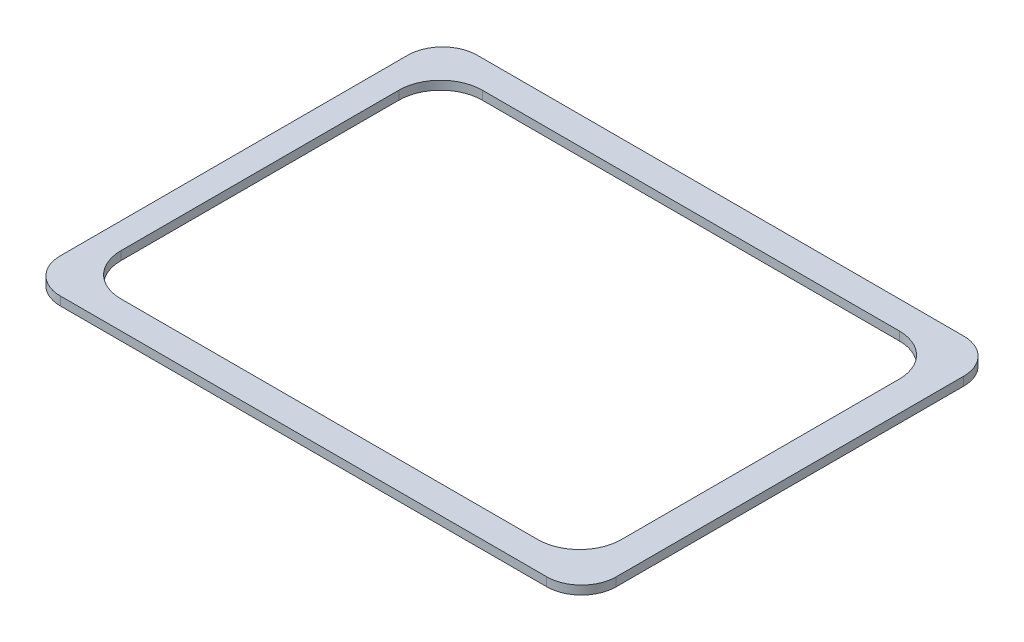
SolidWorks part; units mm, degrees
ref_plane "Front Plane" through (0, 0, 0) normal (0, 0, 1) x (1, 0, 0)
ref_plane "Top Plane" through (0, 0, 0) normal (0, 1, 0) x (1, 0, 0)
ref_plane "Right Plane" through (0, 0, 0) normal (1, 0, 0) x (0, 0, -1)
sketch "Sketch1" plane through (0, 6.35, 0) normal (0, 1, 0) x (1, 0, 0)
  line L19 (90.75, -50.8) -> (90.75, 0)
  line L25 (90.75, -50.8) -> (90.75, 0)
  line L27 (90.75, 0) -> (90.75, 50.8)
  line L44 (101.6, -63.5) -> (101.6, 63.5) construction
  line L45 (88.9, 76.2) -> (-88.9, 76.2) construction
  line L46 (-101.6, 63.5) -> (-101.6, -63.5) construction
  line L47 (-88.9, -76.2) -> (88.9, -76.2) construction
  line L52 (101.6, -63.5) -> (101.6, 63.5)
  line L53 (88.9, 76.2) -> (-88.9, 76.2)
  line L54 (-101.6, 63.5) -> (-101.6, -63.5)
  line L55 (-88.9, -76.2) -> (88.9, -76.2)
  line L168 (90.75, 0) -> (90.75, 50.8)
  line L176 (75.5, 66.05) -> (-76.9, 66.05)
  line L177 (75.5, 66.05) -> (-76.9, 66.05)
  line L178 (-92.15, 50.8) -> (-92.15, -50.8)
  line L179 (-92.15, 50.8) -> (-92.15, -50.8)
  line L180 (-76.9, -66.05) -> (75.5, -66.05)
  line L181 (-76.9, -66.05) -> (75.5, -66.05)
  arc A4 (88.9, -76.2) -> (101.6, -63.5) centre (88.9, -63.5) ccw construction
  arc A6 (101.6, 63.5) -> (88.9, 76.2) centre (88.9, 63.5) ccw construction
  arc A8 (-88.9, 76.2) -> (-101.6, 63.5) centre (-88.9, 63.5) ccw construction
  arc A10 (-101.6, -63.5) -> (-88.9, -76.2) centre (-88.9, -63.5) ccw construction
  arc A16 (88.9, -76.2) -> (101.6, -63.5) centre (88.9, -63.5) ccw
  arc A17 (101.6, 63.5) -> (88.9, 76.2) centre (88.9, 63.5) ccw
  arc A18 (-88.9, 76.2) -> (-101.6, 63.5) centre (-88.9, 63.5) ccw
  arc A19 (-101.6, -63.5) -> (-88.9, -76.2) centre (-88.9, -63.5) ccw
  arc A24 (90.75, 50.8) -> (75.5, 66.05) centre (75.5, 50.8) ccw
  arc A26 (90.75, 50.8) -> (75.5, 66.05) centre (75.5, 50.8) ccw
  arc A132 (-76.9, 66.05) -> (-92.15, 50.8) centre (-76.9, 50.8) ccw
  arc A134 (-76.9, 66.05) -> (-92.15, 50.8) centre (-76.9, 50.8) ccw
  arc A140 (-92.15, -50.8) -> (-76.9, -66.05) centre (-76.9, -50.8) ccw
  arc A141 (-92.15, -50.8) -> (-76.9, -66.05) centre (-76.9, -50.8) ccw
  arc A142 (75.5, -66.05) -> (90.75, -50.8) centre (75.5, -50.8) ccw
  arc A143 (75.5, -66.05) -> (90.75, -50.8) centre (75.5, -50.8) ccw
  dimension "D1" = 3
extrude "FrontFace" add sketch "Sketch1" along normal blind 3.175
equation "\"ShellWallThickness\"=0.115"
equation "\"ShellOverlap\"=0.625"
